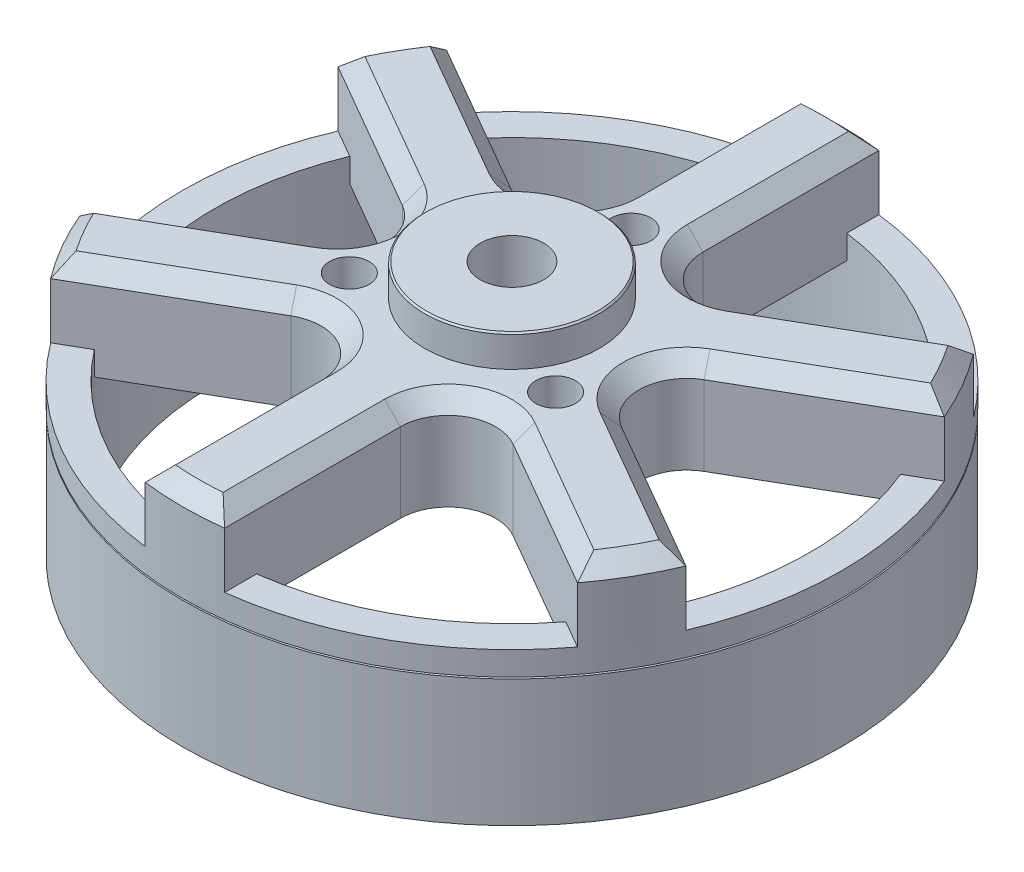
SolidWorks part; units mm, degrees
material "Gray Cast Iron"
ref_plane "Front Plane" through (0, 0, 0) normal (0, 0, 1) x (1, 0, 0)
ref_plane "Top Plane" through (0, 0, 0) normal (0, 1, 0) x (1, 0, 0)
ref_plane "Right Plane" through (0, 0, 0) normal (1, 0, 0) x (0, 0, -1)
sketch "Sketch1" plane through (0, 0, 0) normal (0, 1, 0) x (1, 0, 0)
  circle A0 centre (0, 0) radius 20.75
  circle A1 centre (0, 0) radius 18.75
extrude "Boss-Extrude1" add sketch "Sketch1" along normal blind 8
sketch "Sketch2" plane through (0, 8, 0) normal (0, 1, 0) x (1, 0, 0)
  circle A0 centre (0, 0) radius 18.75
  circle A1 centre (0, 0) radius 20.4
extrude "Boss-Extrude2" add sketch "Sketch2" along normal blind 0.1
sketch "Sketch3" plane through (0, 8.1, 0) normal (0, 1, 0) x (1, 0, 0)
  circle A0 centre (0, 0) radius 20.75
extrude "Boss-Extrude3" add sketch "Sketch3" along normal blind 6
sketch "Sketch4" plane through (0, 14.1, 0) normal (0, 1, 0) x (1, 0, 0)
  circle A0 centre (0, 0) radius 5.5
extrude "Boss-Extrude4" add sketch "Sketch4" along normal blind 2
sketch "Sketch5" plane through (0, 16.1, 0) normal (0, 1, 0) x (1, 0, 0)
  circle A0 centre (0, 0) radius 2
extrude "Cut-Extrude1" cut sketch "Sketch5" against normal blind 22
sketch "Sketch7" plane through (0, 14.1, 0) normal (0, 1, 0) x (1, 0, 0)
  circle A0 centre (0, 0) radius 5.5 construction
  circle A1 centre (0, 0) radius 5.5 construction
  circle A2 centre (0, 7.5) radius 1.25
  point P0 (0, 7.5)
  point P1 (0, 5.5)
  dimension "D1" = 2
extrude "Cut-Extrude2" cut sketch "Sketch7" against normal blind 10
ref_axis "Axis1" through (0, 8, 0) along (0, -1, 0)
pattern_circular "CirPattern1" count 3 over 360 about axis through (0, 8, 0) along (0, -1, 0) of "Cut-Extrude2"
sketch "Sketch8" plane through (0, 14.1, 0) normal (0, 1, 0) x (1, 0, 0)
  line L0 (-7, 6.9282) -> (-16.5891, 12.4645)
  line L1 (2.5, 9.5263) -> (2.5, 20.75)
  line L2 (-2.5, 9.5263) -> (-2.5, 20.75)
  line L3 (-2.5, -9.5263) -> (-2.5, -20.5988)
  line L7 (7, -6.9282) -> (19.8872, -14.3686)
  line L9 (-9.5, -2.5981) -> (-19.0891, -8.1344)
  line L12 (9.5, 2.5981) -> (19.0891, 8.1344)
  line L13 (-9.5, 2.5981) -> (-19.0891, 8.1344)
  line L14 (-7, -6.9282) -> (-16.5891, -12.4645)
  line L15 (2.5, -9.5263) -> (2.5, -20.5988)
  line L16 (9.5, -2.5981) -> (19.0891, -8.1344)
  line L17 (7, 6.9282) -> (16.5891, 12.4645)
  arc A0 (16.5891, 12.4645) -> (-16.5891, 12.4645) centre (0, 0) ccw
  arc A1 (-19.0891, 8.1344) -> (-19.0891, -8.1344) centre (0, 0) ccw
  arc A2 (19.0891, -8.1344) -> (19.0891, 8.1344) centre (0, 0) ccw
  arc A3 (-16.5891, -12.4645) -> (-2.5, -20.5988) centre (0, 0) ccw
  arc A4 (2.5, -20.5988) -> (16.5891, -12.4645) centre (0, 0) ccw
  arc A5 (-2.5, 9.5263) -> (-7, 6.9282) centre (-5.5, 9.5263) cw
  arc A6 (-9.5, 2.5981) -> (-9.5, -2.5981) centre (-11, 0) cw
  arc A7 (-7, -6.9282) -> (-2.5, -9.5263) centre (-5.5, -9.5263) cw
  arc A8 (2.5, -9.5263) -> (7, -6.9282) centre (5.5, -9.5263) cw
  arc A9 (9.5, -2.5981) -> (9.5, 2.5981) centre (11, 0) cw
  arc A10 (7, 6.9282) -> (2.5, 9.5263) centre (5.5, 9.5263) cw
  point P2 (23.4262, 13.5251)
  point P4 (1.25, 2.1651)
  point P5 (21.1372, -12.2035)
  point P6 (2.5, 0)
  point P8 (-2.5, 0)
  point P12 (0, -28.3333)
  point P13 (-26.0364, -15.0321)
  point P14 (-24.9158, 14.3852)
  point P16 (-1.25, 2.1651)
  point P17 (-27.2864, -12.867)
  point P19 (-2.5, -28.3333)
  point P20 (-1.25, -2.1651)
  point P22 (1.25, -2.1651)
  point P23 (24.6762, 11.3601)
  point P24 (-1.25, -2.1651)
  point P25 (-26.1658, 12.2201)
  point P27 (-24.7864, -17.1972)
  point P29 (2.5, -28.3333)
  point P31 (22.3872, -10.0385)
  point P33 (22.1762, 15.6902)
  circle M12 centre (0, 0) radius 20.75
  dimension "D1" = 3
  dimension "D2" = 5
extrude "Cut-Extrude3" cut sketch "Sketch8" against normal blind 4.5 contours A10 L17 L1 M12 | A5 L2 L0 M12 | A6 L13 L9 M12 | A9 L16 L12 M12 | A8 L15 L7 M12 | A7 L14 L3 M12 region at (-7.756, 14.1, -13.4338) region at (-15.512, 14.1, 0) region at (7.756, 14.1, -13.4338) region at (-7.756, 14.1, 13.4338) region at (15.512, 14.1, 0) region at (7.756, 14.1, 13.4338)
sketch "Sketch9" plane through (0, 9.6, 0) normal (0, 1, 0) x (1, 0, 0)
  line L0 (-2.5, 18.5826) -> (-2.5, 9.5263)
  line L1 (-2.5, -9.5263) -> (-2.5, -18.5826)
  line L2 (14.843, 11.4564) -> (7, 6.9282)
  line L3 (-14.843, 11.4564) -> (-7, 6.9282)
  line L4 (-17.343, 7.1262) -> (-9.5, 2.5981)
  line L5 (2.5, 18.5826) -> (2.5, 9.5263)
  line L6 (-9.5, -2.5981) -> (-17.343, -7.1262)
  line L7 (9.5, -2.5981) -> (17.343, -7.1262)
  line L9 (7, -6.9282) -> (14.843, -11.4564)
  line L10 (-14.843, -11.4564) -> (-7, -6.9282)
  line L11 (9.5, 2.5981) -> (17.343, 7.1262)
  line L12 (2.5, -9.5263) -> (2.5, -18.5826)
  arc A0 (2.5, -9.5263) -> (7, -6.9282) centre (5.5, -9.5263) cw
  arc A1 (9.5, -2.5981) -> (9.5, 2.5981) centre (11, 0) cw
  arc A2 (7, 6.9282) -> (2.5, 9.5263) centre (5.5, 9.5263) cw
  arc A3 (-7, 6.9282) -> (-2.5, 9.5263) centre (-5.5, 9.5263) ccw
  arc A4 (-9.5, -2.5981) -> (-9.5, 2.5981) centre (-11, 0) ccw
  arc A5 (-2.5, -9.5263) -> (-7, -6.9282) centre (-5.5, -9.5263) ccw
  arc A6 (-2.5, 18.5826) -> (-14.843, 11.4564) centre (0, 0) ccw
  arc A7 (17.343, -7.1262) -> (17.343, 7.1262) centre (0, 0) ccw
  arc A8 (14.843, 11.4564) -> (2.5, 18.5826) centre (0, 0) ccw
  arc A9 (-17.343, 7.1262) -> (-17.343, -7.1262) centre (0, 0) ccw
  arc A10 (-14.843, -11.4564) -> (-2.5, -18.5826) centre (0, 0) ccw
  arc A11 (2.5, -18.5826) -> (14.843, -11.4564) centre (0, 0) ccw
  dimension "D1" = 3
  dimension "D2" = 3
extrude "Cut-Extrude4" cut sketch "Sketch9" against normal blind 4.5
chamfer "Chamfer1" distance 1 angle 45 6 edges at (0, 14.1, -20.75) (-17.97, 14.1, -10.375) (-17.97, 14.1, 10.375) (0, 14.1, 20.75) (17.97, 14.1, -10.375) (17.97, 14.1, 10.375)
chamfer "Chamfer2" distance 1 angle 45 18 edges at (2.5, 14.1, -14.5587) (-2.5, 14.1, -14.5587) (-4, 14.1, -6.9282) (-11.3582, 14.1, -9.4444) (-13.8582, 14.1, -5.1143) (-8, 14.1, 0) (-13.8582, 14.1, 5.1143) (-11.3582, 14.1, 9.4444) (-4, 14.1, 6.9282) (-2.5, 14.1, 14.5587) (4, 14.1, -6.9282) (11.3582, 14.1, -9.4444) (13.8582, 14.1, -5.1143) (8, 14.1, 0) (13.8582, 14.1, 5.1143) (11.3582, 14.1, 9.4444) (4, 14.1, 6.9282) (2.5, 14.1, 14.5587)
chamfer "Chamfer3" distance 0.1 angle 45 1 edges at (0, 16.1, 5.5)
